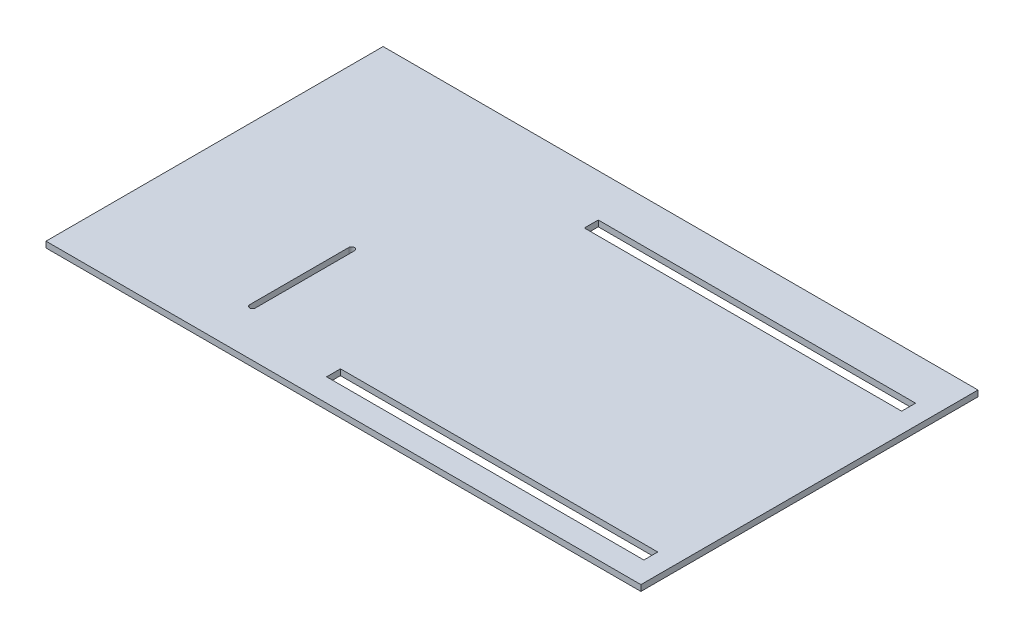
SolidWorks part; units mm, degrees
ref_plane "정면" through (0, 0, 0) normal (0, 0, 1) x (1, 0, 0)
ref_plane "윗면" through (0, 0, 0) normal (0, 1, 0) x (1, 0, 0)
ref_plane "우측면" through (0, 0, 0) normal (1, 0, 0) x (0, 0, -1)
sketch "스케치1" plane through (0, 0, 0) normal (0, 1, 0) x (1, 0, 0)
  line L1 (0, 0) -> (300, 0)
  line L2 (0, 0) -> (0, 170)
  line L3 (0, 170) -> (300, 170)
  line L4 (300, 0) -> (300, 170)
  dimension "D1" = 170
  dimension "D2" = 300
extrude "보스-돌출1" add sketch "스케치1" along normal blind 3
sketch "스케치2" plane through (0, 3, 0) normal (0, 1, 0) x (1, 0, 0)
  line L0 (93, 48.6066) -> (93.0904, 48.6066) construction
  line L1 (93, 46.1066) -> (93, 51.1066) construction
  line L3 (79.1, 48.6066) -> (79.1, 73.6066)
  line L4 (79.1, 23.6066) -> (82, 23.6066)
  line L5 (79.1, 23.6066) -> (79.1, 48.6066)
  line L6 (79.1, 73.6066) -> (82, 73.6066)
  line L7 (82, 23.6066) -> (82, 73.6066)
  line L8 (80.1, 68.7292) -> (80.1, 70.9866) construction
  line L10 (81, 68.7292) -> (81, 70.9866) construction
  dimension "D1" = 1
  dimension "D2" = 1
  dimension "D3" = 25
  dimension "D4" = 25
extrude "컷-돌출1" cut sketch "스케치2" against normal blind 10
sketch "스케치3" plane through (0, 3, 0) normal (0, 1, 0) x (1, 0, 0)
  line L0 (82, 73.6066) -> (79.1, 73.6066) construction
  line L1 (79.1, 23.6066) -> (82, 23.6066) construction
  circle A0 centre (80.55, 73.6066) radius 1.45
  circle A1 centre (80.55, 23.6066) radius 1.45
extrude "컷-돌출2" cut sketch "스케치3" against normal blind 10
sketch "스케치4" plane through (0, 3, 0) normal (0, 1, 0) x (1, 0, 0)
  line L0 (122.6506, 147.5) -> (139.511, 147.5) construction
  line L1 (290, 148.5) -> (130, 148.5)
  line L2 (290, 148.5) -> (290, 141.5)
  line L3 (290, 141.5) -> (130, 141.5)
  line L4 (130, 148.5) -> (130, 141.5)
  line L5 (130, 11.5) -> (290, 11.5)
  line L6 (130, 11.5) -> (130, 18.5)
  line L7 (130, 18.5) -> (290, 18.5)
  line L8 (290, 11.5) -> (290, 18.5)
  line L9 (122.6506, 142.5) -> (139.511, 142.5) construction
  line L10 (122.6506, 17.5) -> (139.511, 17.5) construction
  line L11 (300, 0) -> (300, 170) construction
  line L12 (0, 170) -> (0, 0) construction
  dimension "D1" = 1
  dimension "D2" = 1
  dimension "D3" = 1
  dimension "D4" = 10
  dimension "D5" = 130
extrude "컷-돌출3" cut sketch "스케치4" against normal blind 10
